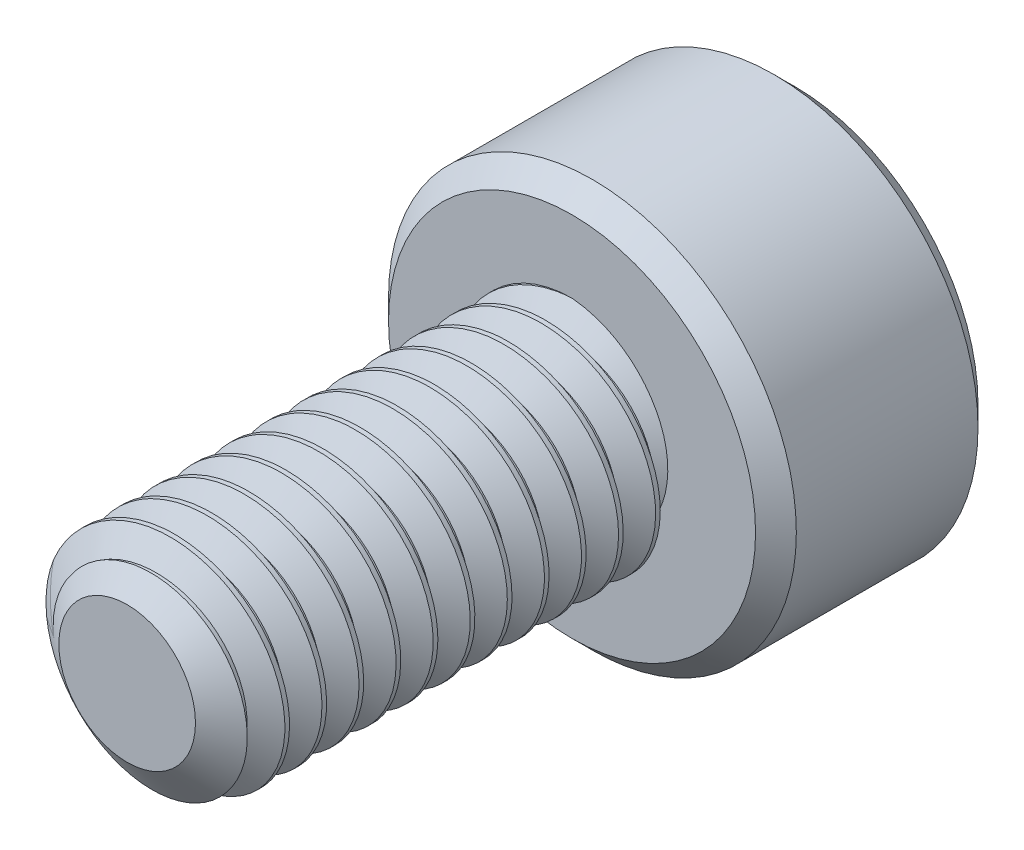
SolidWorks part; units mm, degrees
other "DetailItem1"
ref_plane "Front Plane" through (0, 0, 0) normal (0, 0, 1) x (1, 0, 0)
ref_plane "Top Plane" through (0, 0, 0) normal (0, 1, 0) x (1, 0, 0)
ref_plane "Right Plane" through (0, 0, 0) normal (1, 0, 0) x (0, 0, -1)
sketch "Sketch1" plane through (0, 0, 0) normal (0, 0, 1) x (1, 0, 0)
  circle A0 centre (0, 0) radius 1.5
  dimension "OD" = 3
extrude "Extrude1" add sketch "Sketch1" against normal blind 6
sketch "Sketch2" plane through (0, 0, 0) normal (0, 0, 1) x (1, 0, 0)
  circle A0 centre (0, 0) radius 1.5 construction
  circle A1 centre (0, 0) radius 1.5
curve "Helix/Spiral1" pitch 0.5 height 6.5 radius 1.5 centre (0, 0, 0) axis (0, 0, -1) start towards (0, 1, 0) parameters "pitch"=0.5
sketch "Sketch3" plane through (0, 0, 0) normal (1, 0, 0) x (0, 0, -1)
  line L0 (-0.4375, 1.5) -> (-0.25, 1.1752)
  line L1 (-0.25, 1.1752) -> (-0.1875, 1.1752)
  line L2 (-0.1875, 1.1752) -> (0, 1.5)
  line L3 (-0.4375, 1.5) -> (0, 1.5)
  line L4 (-0.2187, 1.5) -> (-0.2187, 1.1752) construction
  line L5 (-0.3437, 1.3376) -> (-0.0937, 1.3376) construction
  line L6 (0, 1.5) -> (0, -1.5) construction
  dimension "D1" = 0.0625
  dimension "D2" = 0.25
  dimension "D3" = 60
sweep "Cut-Sweep1" cut profiles "Sketch3" path "Helix/Spiral1" align with end faces yes
sketch "Sketch4" plane through (0, 0, 0) normal (1, 0, 0) x (0, 0, -1)
  line L0 (0.4053, 1.5) -> (0, 0.9212)
  line L1 (0, 0.9212) -> (0, 1.5)
  line L2 (0.4053, 1.5) -> (0, 1.5)
  line L3 (-0.4375, 1.5) -> (0, 1.5) construction
  line L4 (0, 0) -> (7.0209, 0) construction
  dimension "D1" = 55
  dimension "D2" = 0.254
revolve "Cut-Revolve1" cut sketch "Sketch4" angle 360 about L4
sketch "Sketch6" plane through (0, 0, -6) normal (0, 0, -1) x (-1, 0, 0)
  circle A0 centre (0, 0) radius 2.75
  dimension "head dia" = 5.5
extrude "Extrude2" add sketch "Sketch6" along normal blind 3
sketch "Sketch7" plane through (0, 0, -9) normal (0, 0, -1) x (-1, 0, 0)
  line L1 (0, 1.4434) -> (-1.25, 0.7217)
  line L2 (-1.25, 0.7217) -> (-1.25, -0.7217)
  line L3 (-1.25, -0.7217) -> (0, -1.4434)
  line L4 (0, -1.4434) -> (1.25, -0.7217)
  line L5 (1.25, -0.7217) -> (1.25, 0.7217)
  line L6 (1.25, 0.7217) -> (0, 1.4434)
  circle A0 centre (0, 0) radius 1.25 construction
  dimension "hex dia" = 2.5
extrude "Cut-Extrude1" cut sketch "Sketch7" against normal blind 1.875
sketch "Sketch8" plane through (0, 0, -9) normal (0, 0, -1) x (-1, 0, 0)
  circle A0 centre (0, 0) radius 1.4434
extrude "Cut-Extrude2" cut sketch "Sketch8" against normal through all draft 45
chamfer "Chamfer1" distance 0.275 angle 45 2 edges at (-2.75, 0, -9) (-2.75, 0, -6)
sketch "Sketch10" plane through (0, 0, -6) normal (0, 0, 1) x (1, 0, 0)
  circle A1 centre (0, 0) radius 1.5
  circle A2 centre (0, 0) radius 1.5
  dimension "D1" = 0
ref_plane "Plane1" through (0, 0, -22) normal (0, 0, 1) x (1, 0, 0)
extrude "partial thread" [suppressed] add sketch "Sketch10" along normal up to surface (58 mm away) separate body up to plane "Plane1"
chamfer "Chamfer2" [suppressed] distance 0.06 angle 45
combine bodies "Combine1" [suppressed] operation type add bodies to combine 107 108
sketch "Sketch9" plane through (0, 0, 0) normal (1, 0, 0) x (0, 0, -1)
  line L0 (0, 1.5) -> (0, -1.5) construction
  line L1 (1.25, 1.5) -> (1.25, -1.5) construction
  dimension "D1" = 1.25
equation "\"D3@Helix/Spiral1\" = \"screw length@Extrude1\"+\"pitch@Helix/Spiral1\""
equation "\"D1@Sketch3\" = \"pitch@Helix/Spiral1\"*.125"
equation "\"D2@Sketch3\" = \"pitch@Helix/Spiral1\"*.5"
equation "\"D1@Cut-Extrude1\" = \"hex dia@Sketch7\"*.75"
equation "\"D1@Chamfer1\" = \"head dia@Sketch6\"*.05"
equation "\"D1@Sketch9\" = \"pitch@Helix/Spiral1\"*2.5"
equation "\"D1@Chamfer2\"=\"OD@Sketch1\"*.02"
